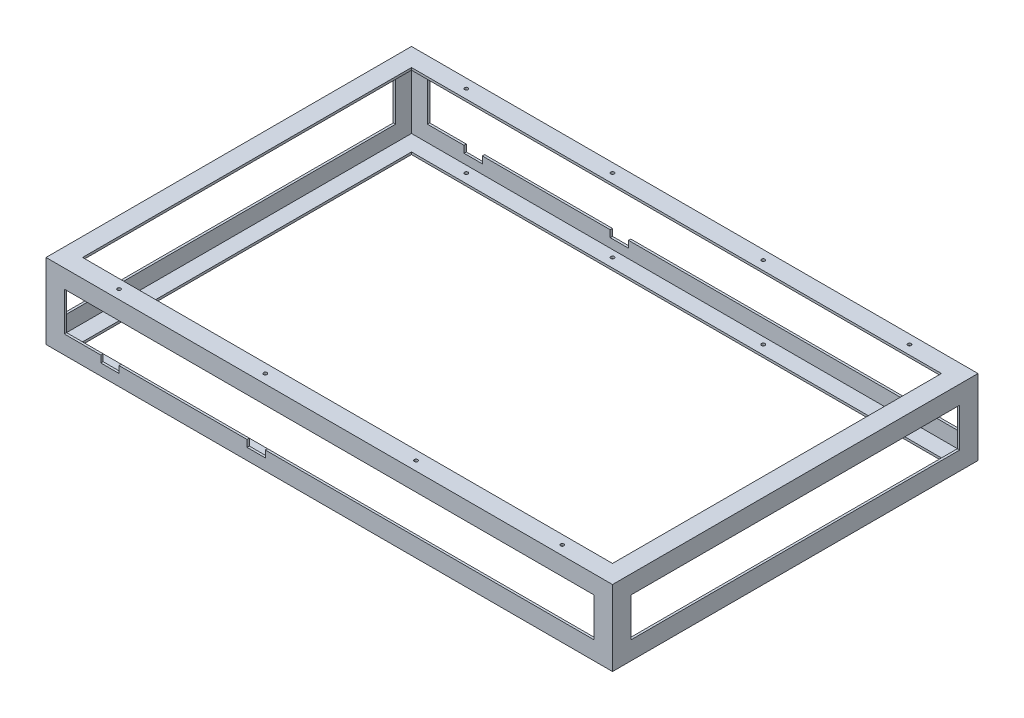
SolidWorks part; units mm, degrees
material "6061 Alloy"
ref_plane "Front Plane" through (0, 0, 0) normal (0, 0, 1) x (1, 0, 0)
ref_plane "Top Plane" through (0, 0, 0) normal (0, 1, 0) x (1, 0, 0)
ref_plane "Right Plane" through (0, 0, 0) normal (1, 0, 0) x (0, 0, -1)
other "Center of Mass"
sketch "Sketch2" plane through (0, 0, 0) normal (1, 0, 0) x (0, 0, -1)
  line L0 (-504.825, -346.075) -> (-504.825, -422.275)
  line L1 (504.825, -422.275) -> (-504.825, -422.275) construction
  line L2 (504.825, -422.275) -> (504.825, 422.275) construction
  line L3 (504.825, 422.275) -> (-504.825, 422.275) construction
  line L4 (-504.825, -422.275) -> (-504.825, 422.275) construction
  line L5 (504.825, -422.275) -> (-504.825, 422.275) construction
  line L6 (504.825, 422.275) -> (-504.825, -422.275) construction
  line L7 (-504.825, -422.275) -> (-428.625, -422.275)
  line L8 (-428.625, -422.275) -> (-428.625, -417.195)
  line L9 (-428.625, -417.195) -> (-498.7519, -417.195)
  line L10 (-498.7519, -417.195) -> (-498.7519, -346.075)
  line L11 (-498.7519, -346.075) -> (-504.825, -346.075)
  line L12 (0, 0) -> (0, -148.4726) construction
  line L13 (0, 0) -> (158.633, 0) construction
  line L14 (498.7519, -417.195) -> (498.7519, -346.075)
  line L15 (428.625, -417.195) -> (498.7519, -417.195)
  line L16 (428.625, -422.275) -> (428.625, -417.195)
  line L17 (504.825, -422.275) -> (428.625, -422.275)
  line L18 (504.825, -346.075) -> (504.825, -422.275)
  line L19 (498.7519, -346.075) -> (504.825, -346.075)
  line L20 (428.625, 417.195) -> (498.7519, 417.195)
  line L21 (428.625, 422.275) -> (428.625, 417.195)
  line L22 (504.825, 422.275) -> (428.625, 422.275)
  line L23 (504.825, 346.075) -> (504.825, 422.275)
  line L24 (498.7519, 346.075) -> (504.825, 346.075)
  line L25 (498.7519, 417.195) -> (498.7519, 346.075)
  line L26 (-498.7519, 417.195) -> (-498.7519, 346.075)
  line L27 (-428.625, 417.195) -> (-498.7519, 417.195)
  line L28 (-428.625, 422.275) -> (-428.625, 417.195)
  line L29 (-504.825, 422.275) -> (-428.625, 422.275)
  line L30 (-504.825, 346.075) -> (-504.825, 422.275)
  line L31 (-498.7519, 346.075) -> (-504.825, 346.075)
  point P0 (0, 0)
  dimension "D1" = 1009.65
  dimension "D2" = 844.55
  dimension "D3" = 76.2
  dimension "D4" = 5.08
extrude "OAL Lenth" [suppressed] add sketch "Sketch2" along normal blind 1574.8
sketch "Sketch3" [suppressed] plane through (0, 0, 0) normal (0, 0, 1) x (1, 0, 0)
  line L0 (0, -422.275) -> (0, -346.075)
  line L1 (1574.8, -346.075) -> (0, -346.075) construction
  line L2 (0, -346.075) -> (0, -422.275) construction
  line L3 (0, -346.075) -> (5.08, -346.075)
  line L4 (5.08, -346.075) -> (5.08, -417.195)
  line L5 (5.08, -417.195) -> (76.2, -417.195)
  line L6 (76.2, -417.195) -> (76.2, -422.275)
  line L7 (1574.8, -422.275) -> (0, -422.275) construction
  line L8 (76.2, -422.275) -> (0, -422.275)
  line L9 (0, 0) -> (697.1877, 0) construction
  line L10 (787.4, 346.075) -> (787.4, -346.075) construction
  line L11 (1574.8, 346.075) -> (0, 346.075) construction
  line L12 (76.2, 422.275) -> (0, 422.275)
  line L13 (76.2, 417.195) -> (76.2, 422.275)
  line L14 (5.08, 417.195) -> (76.2, 417.195)
  line L15 (5.08, 346.075) -> (5.08, 417.195)
  line L16 (0, 346.075) -> (5.08, 346.075)
  line L17 (0, 422.275) -> (0, 346.075)
  line L18 (1574.8, 422.275) -> (1574.8, 346.075)
  line L19 (1574.8, 346.075) -> (1569.72, 346.075)
  line L20 (1569.72, 346.075) -> (1569.72, 417.195)
  line L21 (1569.72, 417.195) -> (1498.6, 417.195)
  line L22 (1498.6, 417.195) -> (1498.6, 422.275)
  line L23 (1498.6, 422.275) -> (1574.8, 422.275)
  line L24 (1498.6, -422.275) -> (1574.8, -422.275)
  line L25 (1498.6, -417.195) -> (1498.6, -422.275)
  line L26 (1569.72, -417.195) -> (1498.6, -417.195)
  line L27 (1569.72, -346.075) -> (1569.72, -417.195)
  line L28 (1574.8, -346.075) -> (1569.72, -346.075)
  line L29 (1574.8, -422.275) -> (1574.8, -346.075)
  dimension "D1" = 5.08
extrude "OAL Width" [suppressed] add sketch "Sketch3" along normal up to surface and the other way up to surface
sketch "Sketch4" [suppressed] plane through (0, 422.275, 0) normal (0, 1, 0) x (1, 0, 0)
  line L0 (0, 504.825) -> (0, 428.625)
  line L1 (0, -428.625) -> (0, -504.825) construction
  line L2 (0, 428.625) -> (5.08, 428.625)
  line L3 (5.08, 428.625) -> (5.08, 499.745)
  line L4 (5.08, 499.745) -> (76.2, 499.745)
  line L5 (76.2, 499.745) -> (76.2, 504.825)
  line L6 (0, 504.825) -> (1574.8, 504.825) construction
  line L7 (76.2, 504.825) -> (0, 504.825)
  line L8 (0, 0) -> (1574.8, 0) construction
  line L9 (1574.8, -428.625) -> (1574.8, -504.825) construction
  line L10 (787.4, 0) -> (787.4, 504.825) construction
  line L11 (76.2, -504.825) -> (0, -504.825)
  line L12 (76.2, -499.745) -> (76.2, -504.825)
  line L13 (5.08, -499.745) -> (76.2, -499.745)
  line L14 (5.08, -428.625) -> (5.08, -499.745)
  line L15 (0, -428.625) -> (5.08, -428.625)
  line L16 (0, -504.825) -> (0, -428.625)
  line L17 (1574.8, -504.825) -> (1574.8, -428.625)
  line L18 (1574.8, -428.625) -> (1569.72, -428.625)
  line L19 (1569.72, -428.625) -> (1569.72, -499.745)
  line L20 (1569.72, -499.745) -> (1498.6, -499.745)
  line L21 (1498.6, -499.745) -> (1498.6, -504.825)
  line L22 (1498.6, -504.825) -> (1574.8, -504.825)
  line L23 (1498.6, 504.825) -> (1574.8, 504.825)
  line L24 (1498.6, 499.745) -> (1498.6, 504.825)
  line L25 (1569.72, 499.745) -> (1498.6, 499.745)
  line L26 (1569.72, 428.625) -> (1569.72, 499.745)
  line L27 (1574.8, 428.625) -> (1569.72, 428.625)
  line L28 (1574.8, 504.825) -> (1574.8, 428.625)
  dimension "D1" = 5.08
  dimension "D2" = 76.2
extrude "OAL Height" [suppressed] add sketch "Sketch4" against normal through all
sketch "Sketch5" plane through (0, 0, 0) normal (1, 0, 0) x (0, 0, -1)
  line L0 (0, 304.8) -> (0, -304.8) construction
  line L1 (-508, -304.8) -> (508, -304.8) construction
  line L2 (-508, -304.8) -> (-508, -254)
  line L3 (-508, -304.8) -> (-457.2, -304.8)
  line L4 (-457.2, -304.8) -> (-457.2, -298.45)
  line L5 (-457.2, -298.45) -> (-501.65, -298.45)
  line L6 (-501.65, -298.45) -> (-501.65, -254)
  line L7 (-501.65, -254) -> (-508, -254)
  line L8 (501.65, -254) -> (508, -254)
  line L9 (501.65, -298.45) -> (501.65, -254)
  line L10 (457.2, -298.45) -> (501.65, -298.45)
  line L11 (457.2, -304.8) -> (457.2, -298.45)
  line L12 (508, -304.8) -> (457.2, -304.8)
  line L13 (508, -304.8) -> (508, -254)
  line L14 (0, -200.025) -> (-176.3903, -200.025) construction
  line L15 (-508, -95.25) -> (508, -95.25) construction
  line L16 (508, -95.25) -> (508, -146.05)
  line L17 (508, -95.25) -> (457.2, -95.25)
  line L18 (457.2, -95.25) -> (457.2, -101.6)
  line L19 (457.2, -101.6) -> (501.65, -101.6)
  line L20 (501.65, -101.6) -> (501.65, -146.05)
  line L21 (501.65, -146.05) -> (508, -146.05)
  line L22 (-501.65, -146.05) -> (-508, -146.05)
  line L23 (-501.65, -101.6) -> (-501.65, -146.05)
  line L24 (-457.2, -101.6) -> (-501.65, -101.6)
  line L25 (-457.2, -95.25) -> (-457.2, -101.6)
  line L26 (-508, -95.25) -> (-457.2, -95.25)
  line L27 (-508, -95.25) -> (-508, -146.05)
  point P4 (0, 0)
  point P8 (0, -304.8)
  point P32 (0, -95.25)
  dimension "D1" = 1016
  dimension "D2" = 609.6
  dimension "D3" = 50.8
  dimension "D4" = 6.35
  dimension "D5" = 104.775
extrude "X Angle Lenth" add sketch "Sketch5" along normal blind 1574.8 separate body
sketch "Sketch6" plane through (0, -304.8, 0) normal (0, -1, 0) x (1, 0, 0)
  line L0 (0, 0) -> (1574.8, 0) construction
  line L1 (1574.8, -508) -> (1574.8, 508) construction
  line L2 (1574.8, -508) -> (1524, -508)
  line L3 (1574.8, -508) -> (1574.8, -457.2)
  line L4 (1574.8, -457.2) -> (1568.45, -457.2)
  line L5 (1568.45, -457.2) -> (1568.45, -501.65)
  line L6 (1568.45, -501.65) -> (1524, -501.65)
  line L7 (1524, -501.65) -> (1524, -508)
  line L8 (1524, 501.65) -> (1524, 508)
  line L9 (1568.45, 501.65) -> (1524, 501.65)
  line L10 (1568.45, 457.2) -> (1568.45, 501.65)
  line L11 (1574.8, 457.2) -> (1568.45, 457.2)
  line L12 (1574.8, 508) -> (1574.8, 457.2)
  line L13 (1574.8, 508) -> (1524, 508)
  line L15 (787.4, 0) -> (787.4, 197.6325) construction
  line L16 (0, -508) -> (0, 508) construction
  line L17 (0, 508) -> (50.8, 508)
  line L18 (0, 508) -> (0, 457.2)
  line L19 (0, 457.2) -> (6.35, 457.2)
  line L20 (6.35, 457.2) -> (6.35, 501.65)
  line L21 (6.35, 501.65) -> (50.8, 501.65)
  line L22 (50.8, 501.65) -> (50.8, 508)
  line L23 (50.8, -501.65) -> (50.8, -508)
  line L24 (6.35, -501.65) -> (50.8, -501.65)
  line L25 (6.35, -457.2) -> (6.35, -501.65)
  line L26 (0, -457.2) -> (6.35, -457.2)
  line L27 (0, -508) -> (0, -457.2)
  line L28 (0, -508) -> (50.8, -508)
  point P3 (787.4, 0)
  point P6 (1574.8, 0)
  point P32 (0, 0)
  dimension "D1" = 50.8
  dimension "D2" = 6.35
  dimension "D3" = 1016
  dimension "D4" = 1574.8
extrude "Y Angle Lenth" add sketch "Sketch6" against normal blind 209.55
sketch "Sketch15" plane through (0, 0, 0) normal (0, 0, 1) x (1, 0, 0)
  line L0 (0, -254) -> (0, -304.8)
  line L1 (0, -95.25) -> (1574.8, -95.25) construction
  line L2 (787.4, -95.25) -> (787.4, 43.9233) construction
  line L3 (1568.45, -254) -> (1574.8, -254)
  line L4 (1568.45, -298.45) -> (1568.45, -254)
  line L5 (1524, -298.45) -> (1568.45, -298.45)
  line L6 (1524, -304.8) -> (1524, -298.45)
  line L7 (0, -304.8) -> (50.8, -304.8)
  line L8 (50.8, -304.8) -> (50.8, -298.45)
  line L9 (50.8, -298.45) -> (6.35, -298.45)
  line L10 (6.35, -298.45) -> (6.35, -254)
  line L11 (6.35, -254) -> (0, -254)
  line L12 (1574.8, -304.8) -> (1524, -304.8)
  line L13 (1574.8, -254) -> (1574.8, -304.8)
  line L20 (787.4, -95.25) -> (787.4, -304.8) construction
  line L21 (1574.8, -304.8) -> (0, -304.8) construction
  line L24 (787.4, -200.025) -> (896.4031, -200.025) construction
  line L27 (1574.8, -146.05) -> (1574.8, -95.25)
  line L28 (1574.8, -95.25) -> (1524, -95.25)
  line L29 (1524, -95.25) -> (1524, -101.6)
  line L30 (1524, -101.6) -> (1568.45, -101.6)
  line L31 (1568.45, -101.6) -> (1568.45, -146.05)
  line L32 (1568.45, -146.05) -> (1574.8, -146.05)
  line L33 (18.8814, -200.025) -> (113.1502, -200.025) construction
  line L35 (6.35, -146.05) -> (0, -146.05)
  line L36 (6.35, -101.6) -> (6.35, -146.05)
  line L37 (50.8, -101.6) -> (6.35, -101.6)
  line L38 (50.8, -95.25) -> (50.8, -101.6)
  line L39 (0, -95.25) -> (50.8, -95.25)
  line L40 (0, -146.05) -> (0, -95.25)
  dimension "D1" = 50.8
  dimension "D2" = 6.35
extrude "Z Angle Lenth" add sketch "Sketch15" against normal up to surface and the other way up to surface up to face at (787.4, -200.025, -508) other way up to face at (787.4, -200.025, 508)
sketch "Sketch16" plane through (0, -95.25, 0) normal (0, 1, 0) x (1, 0, 0)
  line L0 (1409.7, 0) -> (1409.7, 482.6) construction
  line L1 (0, 508) -> (0, -508) construction
  line L2 (1003.3, 0) -> (1003.3, 482.6) construction
  line L3 (584.2, 0) -> (584.2, 482.6) construction
  line L4 (177.8, 0) -> (177.8, 482.6) construction
  line L5 (177.8, 482.6) -> (584.2, 482.6) construction
  line L6 (584.2, 482.6) -> (1003.3, 482.6) construction
  line L7 (1003.3, 482.6) -> (1409.7, 482.6) construction
  line L8 (1409.7, 0) -> (0, 0) construction
  line L9 (1003.3, -482.6) -> (1409.7, -482.6) construction
  line L10 (584.2, -482.6) -> (1003.3, -482.6) construction
  line L11 (177.8, -482.6) -> (584.2, -482.6) construction
  line L12 (0, 508) -> (1574.8, 508) construction
  circle A0 centre (1409.7, 482.6) radius 4.7625
  circle A1 centre (1003.3, 482.6) radius 4.7625
  circle A2 centre (584.2, 482.6) radius 4.7625
  circle A3 centre (177.8, 482.6) radius 4.7625
  circle A4 centre (177.8, -482.6) radius 4.7625
  circle A5 centre (584.2, -482.6) radius 4.7625
  circle A6 centre (1003.3, -482.6) radius 4.7625
  circle A7 centre (1409.7, -482.6) radius 4.7625
  point P2 (0, 0)
  point P24 (0, 0)
  point P26 (177.8, 0)
  point P27 (584.2, 0)
  point P28 (1003.3, 0)
  point P29 (1409.7, 0)
  point P30 (177.8, 481.89)
  dimension "D1" = 9.525
  dimension "D2" = 177.8
  dimension "D3" = 406.4
  dimension "D4" = 406.4
  dimension "D5" = 419.1
  dimension "D6" = 25.4
extrude "Wheel Mount LOC Holes" cut sketch "Sketch16" against normal through all
sketch "Sketch17" plane through (0, 0, 508) normal (0, 0, 1) x (1, 0, 0)
  line L0 (1524, -254) -> (50.8, -254) construction
  line L1 (203.2, -273.05) -> (152.4, -273.05)
  line L2 (203.2, -273.05) -> (203.2, -234.95)
  line L3 (203.2, -234.95) -> (152.4, -234.95)
  line L4 (152.4, -273.05) -> (152.4, -234.95)
  line L5 (203.2, -273.05) -> (152.4, -234.95) construction
  line L6 (203.2, -234.95) -> (152.4, -273.05) construction
  line L7 (0, -95.25) -> (0, -304.8) construction
  line L8 (609.6, -273.05) -> (609.6, -234.95)
  line L9 (609.6, -273.05) -> (558.8, -273.05)
  line L10 (558.8, -273.05) -> (558.8, -234.95)
  line L11 (609.6, -234.95) -> (558.8, -234.95)
  point P0 (177.8, -254)
  dimension "D1" = 50.8
  dimension "D2" = 19.05
  dimension "D3" = 177.8
  dimension "D4" = 2
extrude "Front Control Arm Cutouts" cut sketch "Sketch17" against normal through all
sketch "Sketch18" plane through (0, -95.25, 0) normal (0, 1, 0) x (1, 0, 0)
  line L0 (1003.3, -482.6) -> (1030.6685, -482.6) construction
